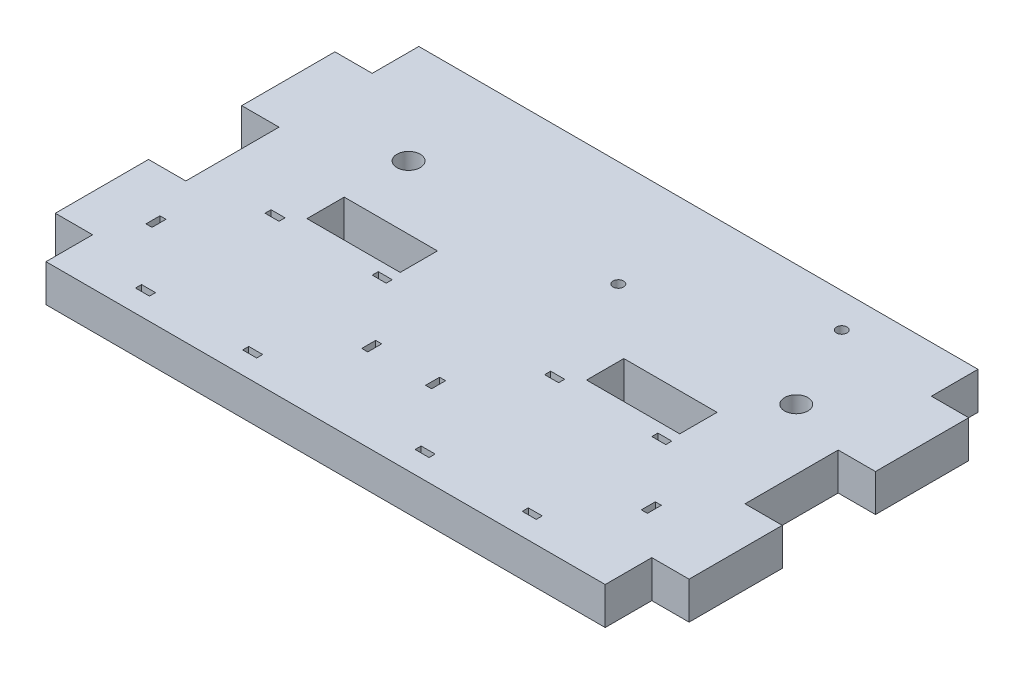
SolidWorks part; units mm, degrees
ref_plane "Front Plane" through (0, 0, 0) normal (0, 0, 1) x (1, 0, 0)
ref_plane "Top Plane" through (0, 0, 0) normal (0, 1, 0) x (1, 0, 0)
ref_plane "Right Plane" through (0, 0, 0) normal (1, 0, 0) x (0, 0, -1)
sketch "Sketch1" plane through (0, 0, 0) normal (0, 1, 0) x (1, 0, 0)
  line L0 (-66.0627, 0) -> (65.2437, 0) construction
  line L1 (-60, 40) -> (60, 40)
  line L2 (-60, 40) -> (-60, -40)
  line L3 (-60, -40) -> (60, -40)
  line L4 (60, 40) -> (60, -40)
  line L5 (27.5, -7.5) -> (27.5, -34) construction
  line L6 (5, -7.5) -> (50, -7.5) construction
  line L7 (5, -7.5) -> (5, -34) construction
  line L8 (5, -34) -> (50, -34) construction
  line L9 (50, -7.5) -> (50, -34) construction
  line L10 (-5.21, 35.09) -> (40, 35.09) construction
  line L11 (-5.21, 35.09) -> (-5.21, 15) construction
  line L12 (-5.21, 15) -> (40, 15) construction
  line L13 (40, 35.09) -> (40, 15) construction
  line L14 (-5.21, 35.09) -> (40, 15) construction
  line L15 (-5.21, 15) -> (40, 35.09) construction
  line L16 (5, -20.75) -> (50, -20.75) construction
  line L17 (14.5, -35.3) -> (17.5, -35.3)
  line L18 (14.5, -7.5) -> (17.5, -7.5)
  line L19 (14.5, -7.5) -> (14.5, -6.2)
  line L20 (14.5, -6.2) -> (17.5, -6.2)
  line L21 (17.5, -7.5) -> (17.5, -6.2)
  line L22 (17.5, -34) -> (17.5, -35.3)
  line L23 (14.5, -34) -> (17.5, -34)
  line L24 (14.5, -34) -> (14.5, -35.3)
  line L25 (40.5, -7.5) -> (40.5, -6.2)
  line L26 (40.5, -6.2) -> (37.5, -6.2)
  line L27 (40.5, -7.5) -> (37.5, -7.5)
  line L28 (37.5, -7.5) -> (37.5, -6.2)
  line L29 (40.5, -34) -> (40.5, -35.3)
  line L30 (37.5, -34) -> (37.5, -35.3)
  line L31 (40.5, -34) -> (37.5, -34)
  line L32 (40.5, -35.3) -> (37.5, -35.3)
  line L33 (51.3, -22.25) -> (50, -22.25)
  line L34 (3.7, -19.25) -> (5, -19.25)
  line L35 (3.7, -19.25) -> (3.7, -22.25)
  line L36 (3.7, -22.25) -> (5, -22.25)
  line L37 (5, -19.25) -> (5, -22.25)
  line L38 (51.3, -19.25) -> (50, -19.25)
  line L39 (51.3, -19.25) -> (51.3, -22.25)
  line L40 (50, -19.25) -> (50, -22.25)
  line L41 (-2.5, -62.4684) -> (-2.5, 56.3378) construction
  line L42 (-42.323, 17.6273) -> (-60, 17.6273) construction
  line L44 (-40, 4) -> (-24.658, 4) construction
  line L45 (-39.823, 20.1273) -> (-39.823, 4) construction
  line L46 (40, 4) -> (68, 4) construction
  line L48 (-55, -19.25) -> (-55, -22.25)
  line L49 (-56.3, -19.25) -> (-56.3, -22.25)
  line L50 (-56.3, -19.25) -> (-55, -19.25)
  line L51 (-10, -19.25) -> (-10, -22.25)
  line L52 (-8.7, -22.25) -> (-10, -22.25)
  line L53 (-8.7, -19.25) -> (-8.7, -22.25)
  line L54 (-8.7, -19.25) -> (-10, -19.25)
  line L55 (-56.3, -22.25) -> (-55, -22.25)
  line L56 (-45.5, -35.3) -> (-42.5, -35.3)
  line L57 (-45.5, -34) -> (-42.5, -34)
  line L58 (-42.5, -34) -> (-42.5, -35.3)
  line L59 (-45.5, -34) -> (-45.5, -35.3)
  line L60 (-42.5, -7.5) -> (-42.5, -6.2)
  line L61 (-45.5, -7.5) -> (-42.5, -7.5)
  line L62 (-45.5, -6.2) -> (-42.5, -6.2)
  line L63 (-45.5, -7.5) -> (-45.5, -6.2)
  line L64 (-19.5, -34) -> (-19.5, -35.3)
  line L65 (-19.5, -34) -> (-22.5, -34)
  line L66 (-22.5, -34) -> (-22.5, -35.3)
  line L67 (-22.5, -7.5) -> (-22.5, -6.2)
  line L68 (-19.5, -6.2) -> (-22.5, -6.2)
  line L69 (-19.5, -7.5) -> (-19.5, -6.2)
  line L70 (-19.5, -7.5) -> (-22.5, -7.5)
  line L71 (-19.5, -35.3) -> (-22.5, -35.3)
  circle A0 centre (-39.823, 17.6273) radius 2.5
  circle A1 centre (47, 14) radius 2.5
  circle A2 centre (38.07, 32.68) radius 1.13
  circle A3 centre (5.56, 17.26) radius 1.13
  point P4 (60, 0)
  point P6 (0, 40)
  point P23 (17.395, 25.045)
  point P46 (5, -20.75)
  dimension "D5" = 10
  dimension "D10" = 15
  dimension "D17" = 2.26
  dimension "D18" = 2.26
  dimension "D11" = 5
  dimension "D12" = 5
  dimension "D23" = 13
  dimension "D24" = 10
  dimension "D1" = 120
  dimension "D2" = 80
  dimension "D3" = 26.5
  dimension "D4" = 45
  dimension "D6" = 7.5
  dimension "D7" = 20
  dimension "D8" = 1.3
  dimension "D9" = 3
  dimension "D13" = 45.21
  dimension "D14" = 20.09
  dimension "D15" = 15
  dimension "D16" = 20
  dimension "D19" = 15.42
  dimension "D20" = 17.68
  dimension "D21" = 32.51
  dimension "D22" = 1.93
extrude "Boss-Extrude1" add sketch "Sketch1" along normal blind 8
sketch "Sketch2" plane through (0, 0, 0) normal (0, -1, 0) x (1, 0, 0)
  line L1 (7.8694, -17.26) -> (6.7147, -15.26)
  line L2 (6.7147, -15.26) -> (4.4053, -15.26)
  line L3 (4.4053, -15.26) -> (3.2506, -17.26)
  line L4 (3.2506, -17.26) -> (4.4053, -19.26)
  line L5 (4.4053, -19.26) -> (6.7147, -19.26)
  line L6 (6.7147, -19.26) -> (7.8694, -17.26)
  line L7 (40.3794, -32.68) -> (39.2247, -30.68)
  line L8 (39.2247, -30.68) -> (36.9153, -30.68)
  line L9 (36.9153, -30.68) -> (35.7606, -32.68)
  line L10 (35.7606, -32.68) -> (36.9153, -34.68)
  line L11 (36.9153, -34.68) -> (39.2247, -34.68)
  line L12 (39.2247, -34.68) -> (40.3794, -32.68)
  circle A0 centre (5.56, -17.26) radius 2 construction
  circle A1 centre (5.56, -17.26) radius 1.13 construction
  circle A2 centre (38.07, -32.68) radius 2 construction
  circle A3 centre (38.07, -32.68) radius 1.13 construction
  dimension "D1" = 4
  dimension "D2" = 4
extrude "Cut-Extrude1" cut sketch "Sketch2" against normal blind 4
sketch "Sketch3" plane through (0, 0, 0) normal (0, -1, 0) x (1, 0, 0)
  line L0 (-71.3423, 0) -> (66.6402, 0) construction
  line L1 (-40, 4) -> (-20, 4)
  line L2 (-40, 4) -> (-40, -4)
  line L3 (-40, -4) -> (-20, -4)
  line L4 (-20, 4) -> (-20, -4)
  point P7 (-20, 0)
  dimension "D1" = 8
  dimension "D2" = 20
  dimension "D3" = 20
extrude "Cut-Extrude2" cut sketch "Sketch3" against normal up to next
ref_plane "Plane1" through (0, 0, 0) normal (-1, 0, 0) x (0, 0, 1)
mirror "Mirror1" about plane through (0, 0, 0) normal (-1, 0, 0) of "Cut-Extrude2"
sketch "Sketch4" plane through (-60, 0, 0) normal (-1, 0, 0) x (0, 0, 1)
  line L0 (-40, 8) -> (40, 8) construction
  line L1 (30, 8) -> (10, 8)
  line L2 (30, 8) -> (30, 0)
  line L3 (30, 0) -> (10, 0)
  line L4 (10, 8) -> (10, 0)
  line L5 (-40, 0) -> (40, 0) construction
  line L6 (0, 18.5092) -> (0, -11.2621) construction
  line L7 (-10, 8) -> (-10, 0)
  line L8 (-30, 0) -> (-10, 0)
  line L9 (-30, 8) -> (-30, 0)
  line L10 (-30, 8) -> (-10, 8)
  dimension "D1" = 20
  dimension "D2" = 20
extrude "Boss-Extrude2" add sketch "Sketch4" along normal blind 8
mirror "Mirror2" about plane through (0, 0, 0) normal (-1, 0, 0) of "Boss-Extrude2"
